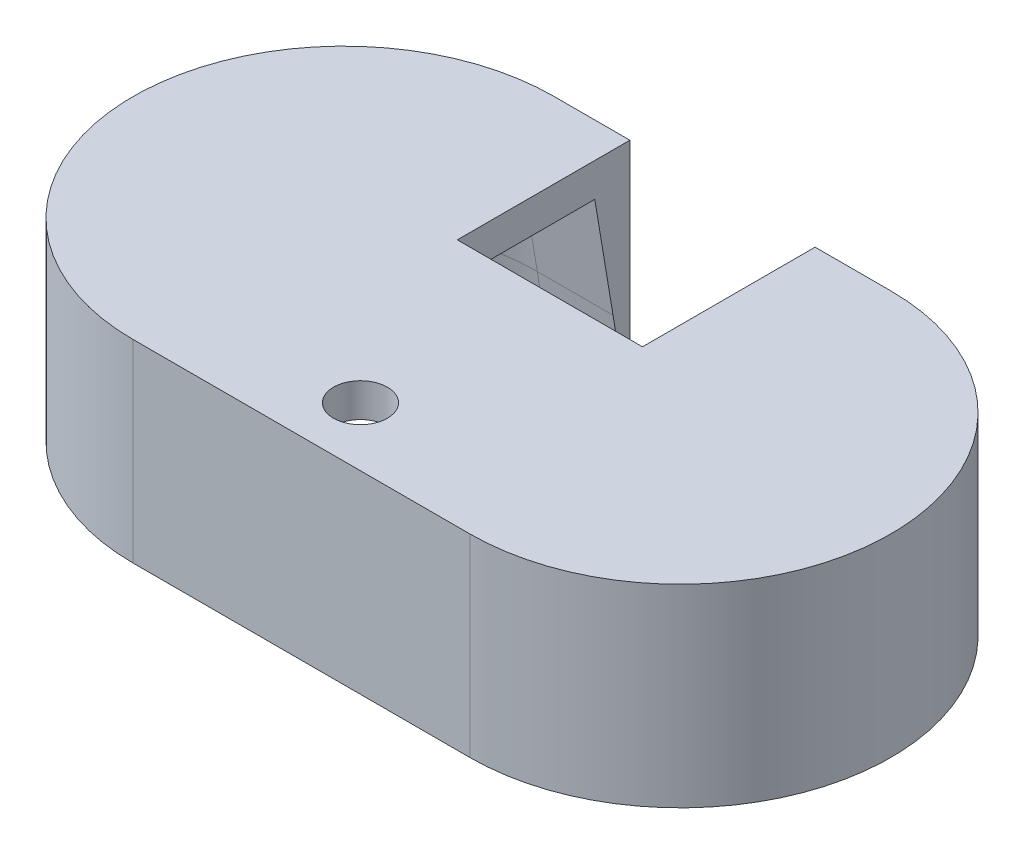
SolidWorks part; units mm, degrees
ref_plane "Front Plane" through (0, 0, 0) normal (0, 0, 1) x (1, 0, 0)
ref_plane "Top Plane" through (0, 0, 0) normal (0, 1, 0) x (1, 0, 0)
ref_plane "Right Plane" through (0, 0, 0) normal (1, 0, 0) x (0, 0, -1)
sketch "Sketch1" plane through (0, 0, 0) normal (0, 1, 0) x (1, 0, 0)
  line L0 (-10, 0) -> (10, 0)
  line L1 (10, 0) -> (22.5, 0)
  line L2 (10, 12.5) -> (-10, 12.5)
  line L3 (0, 12.5) -> (0, -12.5)
  line L4 (0, 17.0334) -> (0, -21.4312) construction
  line L5 (28.146, 0) -> (-33.4676, 0) construction
  line L6 (-10, 0) -> (-22.5, 0)
  line L7 (10, -12.5) -> (-10, -12.5)
  arc A0 (10, -12.5) -> (10, 12.5) centre (10, 0) ccw
  arc A1 (-10, -12.5) -> (-10, 12.5) centre (-10, 0) cw
  point P16 (0, 0)
  dimension "D2" = 12.5
  dimension "D1" = 10
extrude "Boss-Extrude1" add sketch "Sketch1" along normal blind 2 contours A1 L6 L0 L3 L2 | A1 L7 L3 L0 L6 | L1 A0 L2 L3 L0 | L7 A0 L1 L0 L3 region at (-10.1051, 0, -5.7819) region at (-10.1051, 0, 5.7819) region at (10.1051, 0, -5.7819) region at (10.1051, 0, 5.7819)
sketch "Sketch2" plane through (0, 0, 0) normal (0, -1, 0) x (1, 0, 0)
  line L2 (-10, -11.5) -> (10, -11.5)
  line L3 (10, 11.5) -> (-10, 11.5)
  line L4 (-10, -12.5) -> (10, -12.5)
  line L5 (10, 12.5) -> (-10, 12.5)
  line L6 (-10, -12.5) -> (10, -12.5)
  line L7 (10, 12.5) -> (-10, 12.5)
  arc A2 (-10, 11.5) -> (-10, -11.5) centre (-10, 0) ccw
  arc A3 (10, -11.5) -> (10, 11.5) centre (10, 0) ccw
  arc A4 (10, -12.5) -> (10, 12.5) centre (10, 0) ccw
  arc A5 (-10, 12.5) -> (-10, -12.5) centre (-10, 0) ccw
  arc A6 (10, -12.5) -> (10, 12.5) centre (10, 0) ccw
  arc A7 (-10, 12.5) -> (-10, -12.5) centre (-10, 0) ccw
  dimension "D1" = 0
  dimension "D2" = 1
extrude "Boss-Extrude2" add sketch "Sketch2" along normal blind 9.5
chamfer "Chamfer1" distance 0.5 distance2 3 4 edges at (21.5, -9.5, 0) (0, -9.5, 11.5) (0, -9.5, -11.5) (-21.5, -9.5, 0) first distance on face at (0, -9.5, 0)
chamfer "Chamfer2" distance 6.5 distance2 1.0833 4 edges at (21.5, 0, 0) (0, 0, 11.5) (0, 0, -11.5) (-21.5, 0, 0) first distance on face at (15.75, -3.25, 0) first distance on face at (0, -3.25, 11.5) first distance on face at (0, -3.25, -11.5) first distance on face at (-15.75, -3.25, 0)
sketch "Sketch4" plane through (0, 2, 0) normal (0, 1, 0) x (1, 0, 0)
  line L0 (10, 12.5) -> (-10, 12.5) construction
  line L1 (-5.5, 12.5) -> (5.5, 12.5)
  line L2 (-5.5, 12.5) -> (-5.5, 2.25)
  line L3 (-5.5, 2.25) -> (5.5, 2.25)
  line L4 (5.5, 12.5) -> (5.5, 2.25)
  dimension "D1" = 5.5
  dimension "D2" = 11
  dimension "D3" = 10.25
extrude "Cut-Extrude1" cut sketch "Sketch4" against normal through all
sketch "Sketch5" plane through (0, 2, 0) normal (0, 1, 0) x (1, 0, 0)
  line L0 (10, -12.5) -> (-10, -12.5) construction
  circle A0 centre (0, -9) radius 1.6
  dimension "D1" = 3.2
  dimension "D2" = 3.5
extrude "Cut-Extrude2" cut sketch "Sketch5" against normal through all
